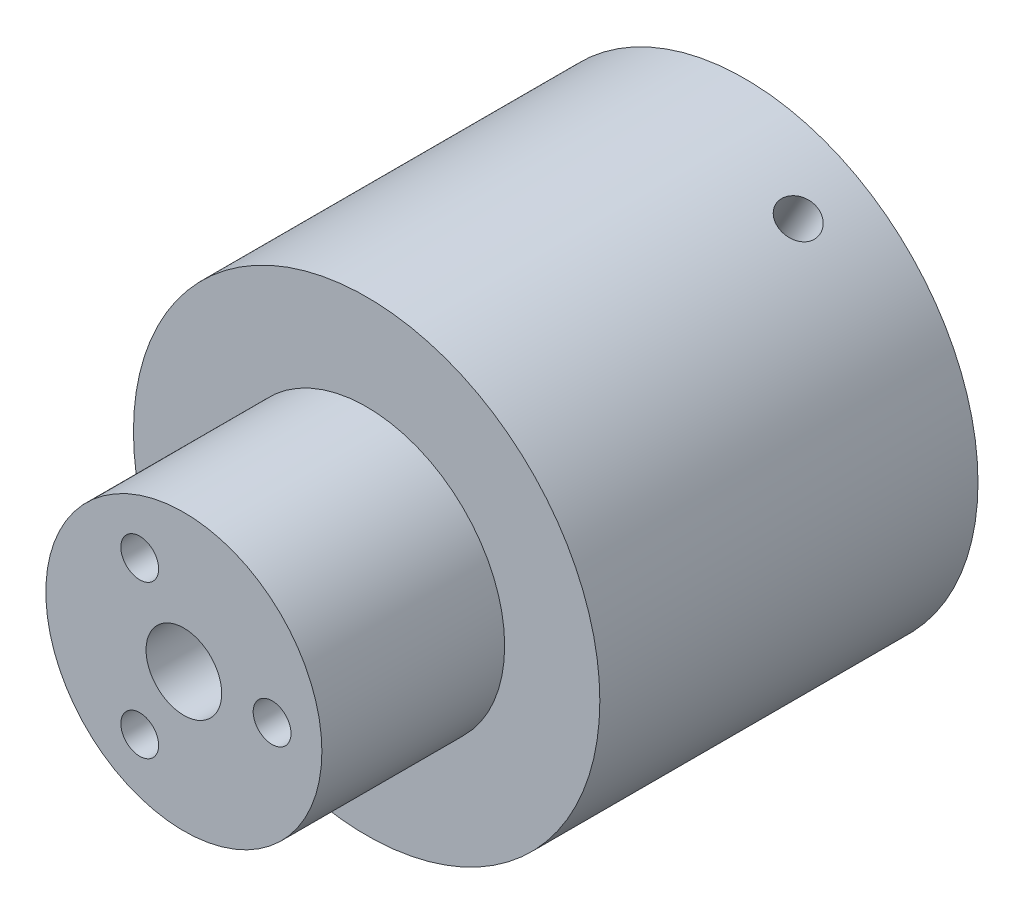
SolidWorks part; units mm, degrees
ref_plane "Front Plane" through (0, 0, 0) normal (0, 0, 1) x (1, 0, 0)
ref_plane "Top Plane" through (0, 0, 0) normal (0, 1, 0) x (1, 0, 0)
ref_plane "Right Plane" through (0, 0, 0) normal (1, 0, 0) x (0, 0, -1)
sketch "Sketch1" plane through (0, 0, 0) normal (0, 0, 1) x (1, 0, 0)
  circle A0 centre (0, 0) radius 18.5
  dimension "D1" = 37
extrude "Boss-Extrude1" add sketch "Sketch1" along normal blind 23
sketch "Sketch2" plane through (0, 0, 23) normal (0, 0, 1) x (1, 0, 0)
  circle A0 centre (0, 0) radius 10.95
  dimension "D1" = 21.9
extrude "Boss-Extrude2" add sketch "Sketch2" along normal blind 3.5 contours A0 | A0 region at (0, 0, 23)
sketch "Sketch4" plane through (0, 0, 0) normal (0, 0, -1) x (-1, 0, 0)
  circle A0 centre (0, 0) radius 3.05
  dimension "D1" = 6.1
extrude "Cut-Extrude1" cut sketch "Sketch4" against normal blind 4.1
sketch "Sketch5" plane through (0, 0, 4.1) normal (0, 0, -1) x (-1, 0, 0)
  circle A0 centre (0, 0) radius 1.5
  dimension "D1" = 3
extrude "Cut-Extrude2" cut sketch "Sketch5" along direction (0, 0, -1) on the side against the normal blind 4 contours A0
sketch "Sketch7" plane through (0, 0, 26.5) normal (0, 0, 1) x (1, 0, 0)
  circle A0 centre (0, 0) radius 3
  circle A1 centre (0, 0) radius 10.95
  dimension "D1" = 21.9
extrude "Boss-Extrude3" add sketch "Sketch7" along normal blind 11
sketch "Sketch9" plane through (0, 0, 37.5) normal (0, 0, 1) x (1, 0, 0)
  line L0 (0, 0) -> (7, 0) construction
  circle A0 centre (7, 0) radius 1.5
  circle A1 centre (-3.5, -6.0622) radius 1.5
  circle A2 centre (-3.5, 6.0622) radius 1.5
  dimension "D2" = 3
  dimension "D1" = 7
  dimension "D3" = 3
extrude "Cut-Extrude4" cut sketch "Sketch9" against normal through all
sketch "Sketch10" plane through (0, 0, 37.5) normal (0, 0, 1) x (1, 0, 0)
  circle A0 centre (0, 0) radius 3
  circle A1 centre (7, 0) radius 3.25
  circle A2 centre (-3.5, 6.0622) radius 3.25
  circle A3 centre (-3.5, -6.0622) radius 3.25
  dimension "D1" = 6.5
extrude "Cut-Extrude5" cut sketch "Sketch10" against normal through all contours A0
sketch "Sketch11" plane through (0, 0, 0) normal (0, 0, -1) x (-1, 0, 0)
  circle A1 centre (3.5, -6.0622) radius 3.25
  circle A2 centre (3.5, -6.0622) radius 3.25
  circle A3 centre (3.5, 6.0622) radius 3.25
  circle A4 centre (3.5, 6.0622) radius 3.25
  circle A5 centre (-7, 0) radius 3.25
  circle A6 centre (-7, 0) radius 3.25
  dimension "D1" = 0
  dimension "D2" = 0
  dimension "D3" = 0
extrude "Cut-Extrude8" cut sketch "Sketch11" against normal blind 30
sketch "Sketch12" plane through (0, 0, 0) normal (0, 0, -1) x (-1, 0, 0)
  circle A0 centre (0, 0) radius 18.5
  circle A1 centre (3.5, 6.0622) radius 3.25
  circle A2 centre (3.5, -6.0622) radius 3.25
  circle A3 centre (-7, 0) radius 3.25
  circle A4 centre (0, 0) radius 3.05
extrude "Boss-Extrude4" add sketch "Sketch12" along normal blind 7
sketch "Sketch13" plane through (0, 0, 0) normal (1, 0, 0) x (0, 0, -1)
  line L0 (7, 0) -> (-3, 0) construction
  circle A0 centre (2, 0) radius 1.5
  dimension "D1" = 3
extrude "Cut-Extrude9" cut sketch "Sketch13" against normal blind 17 from offset 5 offset against normal yes
pattern_circular "CirPattern1" count 3 over 360 about axis through (0, 0, 23) along (0, 0, -1) of "Cut-Extrude9" reverse direction yes
